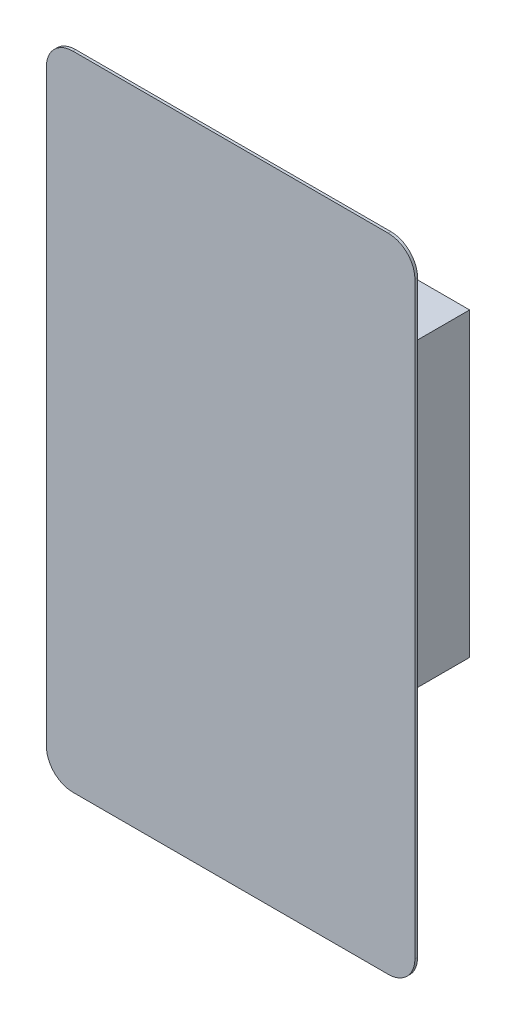
SolidWorks part; units mm, degrees
ref_plane "Front Plane" through (0, 0, 0) normal (0, 0, 1) x (1, 0, 0)
ref_plane "Top Plane" through (0, 0, 0) normal (0, 1, 0) x (1, 0, 0)
ref_plane "Right Plane" through (0, 0, 0) normal (1, 0, 0) x (0, 0, -1)
sketch "Sketch1" plane through (0, 0, 0) normal (0, 0, 1) x (1, 0, 0)
  line L1 (47.4, -96.5) -> (-47.4, -96.5)
  line L2 (55.4, -88.5) -> (55.4, 88.5)
  line L3 (47.4, 96.5) -> (-47.4, 96.5)
  line L4 (-55.4, -88.5) -> (-55.4, 88.5)
  line L5 (55.4, -96.5) -> (-55.4, 96.5) construction
  line L6 (55.4, 96.5) -> (-55.4, -96.5) construction
  arc A0 (47.4, -96.5) -> (55.4, -88.5) centre (47.4, -88.5) ccw
  arc A1 (-47.4, -96.5) -> (-55.4, -88.5) centre (-47.4, -88.5) cw
  arc A2 (-47.4, 96.5) -> (-55.4, 88.5) centre (-47.4, 88.5) ccw
  arc A3 (55.4, 88.5) -> (47.4, 96.5) centre (47.4, 88.5) ccw
  point P0 (0, 0)
  dimension "D3" = 8
  dimension "D1" = 193
  dimension "D2" = 110.8
extrude "Boss-Extrude1" add sketch "Sketch1" against normal blind 0.8
sketch "Sketch2" plane through (0, 0, -0.8) normal (0, 0, -1) x (-1, 0, 0)
  line L0 (-55.4, -88.5) -> (-55.4, 88.5) construction
  line L1 (51.75, -84.85) -> (-48.95, -84.85)
  line L2 (51.75, -84.85) -> (51.75, 81.65)
  line L3 (51.75, 81.65) -> (-48.95, 81.65)
  line L4 (-48.95, -84.85) -> (-48.95, 81.65)
  line L5 (51.75, -84.85) -> (-48.95, 81.65) construction
  line L6 (51.75, 81.65) -> (-48.95, -84.85) construction
  line L8 (-47.4, 96.5) -> (47.4, 96.5) construction
  line L9 (47.4, -96.5) -> (-47.4, -96.5) construction
  line L10 (55.4, 88.5) -> (55.4, -88.5) construction
  point P0 (1.4, -1.6)
  dimension "D1" = 100.7
  dimension "D2" = 166.5
  dimension "D3" = 6.45
  dimension "D4" = 14.85
  dimension "D5" = 11.65
  dimension "D6" = 3.65
extrude "Boss-Extrude2" add sketch "Sketch2" along normal blind 5.3
sketch "Sketch3" plane through (0, 0, -6.1) normal (0, 0, -1) x (-1, 0, 0)
  line L0 (-48.95, 81.65) -> (-48.95, -84.85) construction
  line L1 (31.65, -64.55) -> (-34.05, -64.55) construction
  line L2 (31.65, -64.55) -> (31.65, 61.65) construction
  line L3 (31.65, 61.65) -> (-34.05, 61.65) construction
  line L4 (-34.05, -64.55) -> (-34.05, 61.65) construction
  line L5 (31.65, -64.55) -> (-34.05, 61.65) construction
  line L6 (31.65, 61.65) -> (-34.05, -64.55) construction
  line L7 (-37.95, 54.15) -> (-30.15, 54.15)
  line L8 (-37.95, 54.15) -> (-37.95, 69.15)
  line L9 (-37.95, 69.15) -> (-30.15, 69.15)
  line L10 (-30.15, 54.15) -> (-30.15, 69.15)
  line L11 (-37.95, 54.15) -> (-30.15, 69.15) construction
  line L12 (-37.95, 69.15) -> (-30.15, 54.15) construction
  line L13 (51.75, -84.85) -> (51.75, 81.65) construction
  line L14 (35.55, 54.15) -> (27.75, 54.15)
  line L15 (35.55, 54.15) -> (35.55, 69.15)
  line L16 (35.55, 69.15) -> (27.75, 69.15)
  line L17 (27.75, 54.15) -> (27.75, 69.15)
  line L18 (35.55, 54.15) -> (27.75, 69.15) construction
  line L19 (35.55, 69.15) -> (27.75, 54.15) construction
  line L20 (51.75, 81.65) -> (-48.95, 81.65) construction
  line L21 (-48.95, -84.85) -> (51.75, -84.85) construction
  line L22 (-30.15, -72.05) -> (-37.95, -72.05)
  line L23 (-30.15, -72.05) -> (-30.15, -57.05)
  line L24 (-30.15, -57.05) -> (-37.95, -57.05)
  line L25 (-37.95, -72.05) -> (-37.95, -57.05)
  line L26 (-30.15, -72.05) -> (-37.95, -57.05) construction
  line L27 (-30.15, -57.05) -> (-37.95, -72.05) construction
  line L28 (27.75, -72.05) -> (35.55, -72.05)
  line L29 (27.75, -72.05) -> (27.75, -57.05)
  line L30 (27.75, -57.05) -> (35.55, -57.05)
  line L31 (35.55, -72.05) -> (35.55, -57.05)
  line L32 (27.75, -72.05) -> (35.55, -57.05) construction
  line L33 (27.75, -57.05) -> (35.55, -72.05) construction
  circle A0 centre (-34.05, 61.65) radius 1.5
  circle A1 centre (31.65, 61.65) radius 1.5
  circle A2 centre (31.65, -64.55) radius 1.5
  circle A3 centre (-34.05, -64.55) radius 1.5
  point P0 (-1.2, -1.45)
  dimension "D7" = 3
  dimension "D1" = 11
  dimension "D2" = 7.8
  dimension "D3" = 15
  dimension "D4" = 16.2
  dimension "D5" = 12.5
  dimension "D6" = 12.8
extrude "Boss-Extrude3" add sketch "Sketch3" along normal blind 2.6
sketch "Sketch4" plane through (0, 0, -6.1) normal (0, 0, -1) x (-1, 0, 0)
  line L0 (-48.95, -84.85) -> (51.75, -84.85) construction
  line L1 (-31.75, -41.85) -> (26.75, -41.85)
  line L2 (-31.75, -41.85) -> (-31.75, 48.65)
  line L3 (-31.75, 48.65) -> (26.75, 48.65)
  line L4 (26.75, -41.85) -> (26.75, 48.65)
  line L5 (-31.75, -41.85) -> (26.75, 48.65) construction
  line L6 (-31.75, 48.65) -> (26.75, -41.85) construction
  line L7 (51.75, -84.85) -> (51.75, 81.65) construction
  point P0 (-2.5, 3.4)
  dimension "D1" = 58.5
  dimension "D2" = 90.5
  dimension "D3" = 43
  dimension "D4" = 25
extrude "Boss-Extrude4" add sketch "Sketch4" along normal blind 34
chamfer "Chamfer1" distance 3 angle 45 8 edges at (-31.65, -72.05, -8.7) (-31.65, -57.05, -8.7) (34.05, -72.05, -8.7) (34.05, -57.05, -8.7) (34.05, 54.15, -8.7) (34.05, 69.15, -8.7) (-31.65, 54.15, -8.7) (-31.65, 69.15, -8.7)
sketch "Sketch5" plane through (0, 0, -8.7) normal (0, 0, -1) x (-1, 0, 0)
  line L1 (-34.05, 61.65) -> (31.65, 61.65) construction
  line L2 (-34.05, 61.65) -> (-34.05, -64.55) construction
  line L3 (-34.05, -64.55) -> (31.65, -64.55) construction
  line L4 (31.65, 61.65) -> (31.65, -64.55) construction
